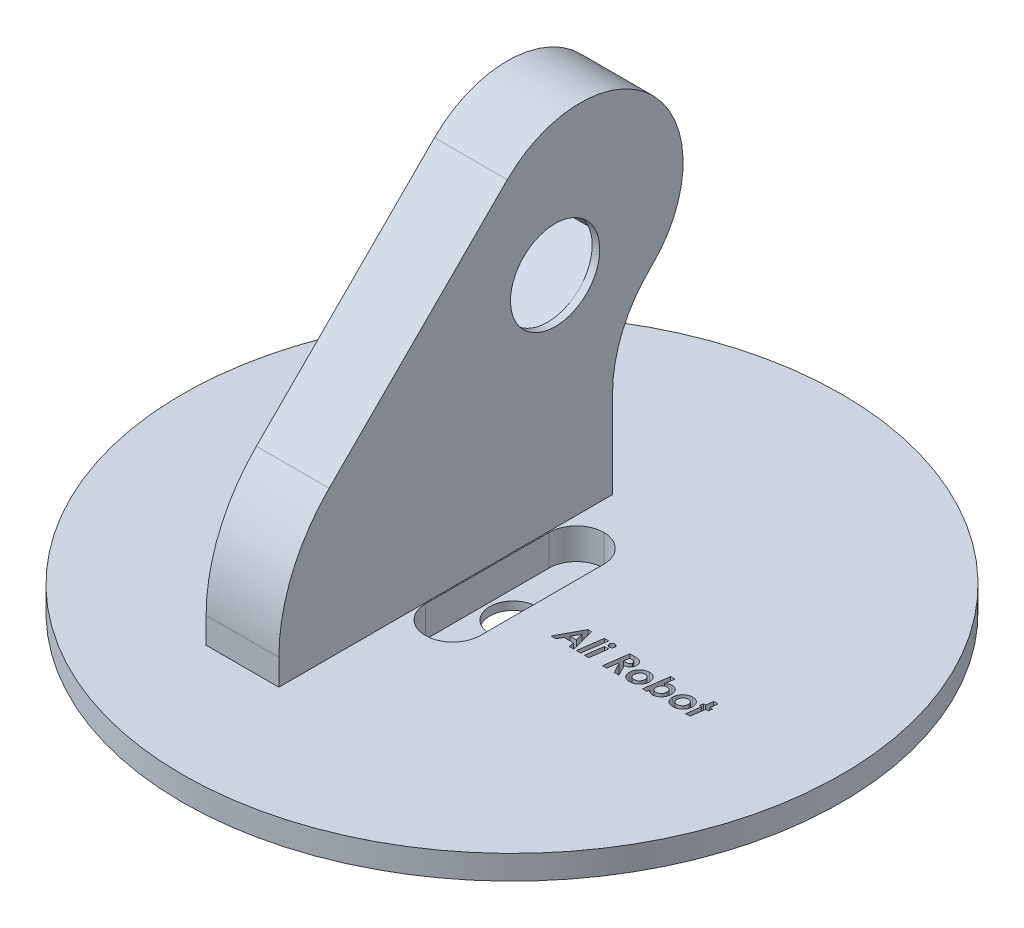
SolidWorks part; units mm, degrees
ref_plane "Front Plane" through (0, 0, 0) normal (0, 0, 1) x (1, 0, 0)
ref_plane "Top Plane" through (0, 0, 0) normal (0, 1, 0) x (1, 0, 0)
ref_plane "Right Plane" through (0, 0, 0) normal (1, 0, 0) x (0, 0, -1)
sketch "Sketch2" plane through (0, 0, 0) normal (0, 1, 0) x (1, 0, 0)
  circle A0 centre (0, 0) radius 48
  dimension "D1" = 96
extrude "Boss-Extrude1" add sketch "Sketch2" along normal blind 3.5
ref_plane "Plane1" through (-4, 0, 0) normal (1, 0, 0) x (0, 0, -1)
sketch "Sketch7" plane through (-4, 0, 0) normal (1, 0, 0) x (0, 0, -1)
  line L0 (18.6521, 16.3561) -> (18.6521, 3.5)
  line L5 (48, 3.5) -> (-48, 3.5) construction
  line L6 (-22.6311, 24.9401) -> (3.3119, 50.8831)
  line L7 (-43.5609, 3.5) -> (18.6521, 3.5)
  line L11 (-29.9535, 3.5) -> (-29.9535, 7.2624)
  arc A4 (24.252, 29.4036) -> (3.3119, 50.8831) centre (13.9185, 40.2765) ccw
  arc A5 (24.252, 29.4036) -> (18.6521, 16.3561) centre (36.6521, 16.3561) ccw
  arc A6 (-22.6311, 24.9401) -> (-29.9535, 7.2624) centre (-4.9535, 7.2624) ccw
  dimension "D1" = 25
  dimension "D4" = 30
  dimension "D3" = 18
  dimension "D5" = 45
extrude "Boss-Extrude2" add sketch "Sketch7" against normal blind 10.6 contours A5 A4 L6 L7 L0 | A4 | A4 | A4 | L6 A6 L7 region at (-4, 25.827, -1.7732)
ref_plane "Plane2" through (-6, 0, 0) normal (1, 0, 0) x (0, 0, -1)
sketch "Sketch31" plane through (-14.6, 10.4618, -5.3595) normal (-1, 0, 0) x (0, 0, 1)
  line L0 (-5.4155, 34.0546) -> (11.7496, 18.7458)
  line L1 (11.7496, 18.7458) -> (3.0968, 9.0438)
  line L2 (3.0968, 9.0438) -> (-14.0683, 24.3526)
  line L3 (-14.0683, 24.3526) -> (-5.4155, 34.0546)
  circle A0 centre (-4.9225, 24.9054) radius 6.5
  dimension "D1" = 6.5
extrude "Cut-Extrude18" cut sketch "Sketch31" against normal through all contours A0
extrude "Cut-Extrude19" cut sketch "Sketch31<3>" against normal blind 9.5 contours L0 L1 L2 L3
sketch "Sketch31<3>" plane through (-14.6, 10.4618, -5.3595) normal (-1, 0, 0) x (0, 0, 1) same geometry as "Sketch31"
sketch "Sketch32" plane through (-14.6, 0, 0) normal (-1, 0, 0) x (0, 0, 1)
  line L0 (6.3901, 29.2076) -> (-2.2627, 19.5056) construction
  circle A0 centre (-17.0806, 41.2645) radius 1
  circle A1 centre (3.9294, 22.6926) radius 1
  arc A3 (-14.6084, 40.2182) -> (-15.5944, 39.1126) centre (-10.282, 35.3672) ccw construction
  dimension "D1" = 2.5
  dimension "D2" = 2.5
extrude "Cut-Extrude20" cut sketch "Sketch32" against normal blind 4.5
sketch "Sketch33" plane through (0, 0, 0) normal (0, -1, 0) x (1, 0, 0)
  circle A0 centre (0, 0) radius 42.5
  dimension "D1" = 85
extrude "Boss-Extrude3" add sketch "Sketch33" along normal blind 2.2
sketch "Sketch34" plane through (-3.9333, 3.5, 15.1139) normal (0, 1, 0) x (1, 0, 0)
  line L1 (0.0806, 2.3531) -> (8.0806, 2.3531)
  line L2 (0.0806, 2.3531) -> (0.0806, 28.3531)
  line L3 (0.0806, 28.3531) -> (8.0806, 28.3531)
  line L4 (8.0806, 2.3531) -> (8.0806, 28.3531)
  dimension "D1" = 26
  dimension "D2" = 8
extrude "Cut-Extrude21" cut sketch "Sketch34" against normal blind 4.5
sketch "Sketch35" plane through (64.9204, 3.5, -6.6124) normal (0, 1, 0) x (1, 0, 0)
  circle A0 centre (-64.8162, -6.541) radius 3.43
  dimension "D1" = 6.86
extrude "Cut-Extrude22" cut sketch "Sketch35" against normal through all
fillet "Fillet1" radius 4 4 edges at (4.1473, 1.25, 12.7608) (-3.8527, 1.25, 12.7608) (4.1473, 1.25, -13.2392) (-3.8527, 1.25, -13.2392)
sketch "Sketch36" plane through (-0.3649, -1, -0.2316) normal (0, 1, 0) x (1, 0, 0)
  circle A0 centre (0.9998, 5.746) radius 1
  circle A1 centre (0.9966, -6.0667) radius 1
  circle A3 centre (0.4691, -0.1602) radius 3.43 construction
  dimension "D1" = 2.5
  dimension "D2" = 2.5
extrude "Cut-Extrude23" cut sketch "Sketch36" against normal blind 4.5
sketch "Sketch37" plane through (0, 3.5, 0) normal (0, 1, 0) x (1, 0, 0)
  line L0 (-48, 0) -> (59.3455, 0) construction
  line L1 (0, -48) -> (0, 73.7974) construction
  circle A0 centre (0, 0) radius 48 construction
sketch "Sketch38" plane through (0, 3.5, 0) normal (0, 1, 0) x (1, 0, 0)
  text T0 "<b><i>Ali Robot</i></b>"
extrude "Cut-Extrude24" cut sketch "Sketch38" against normal blind 3
